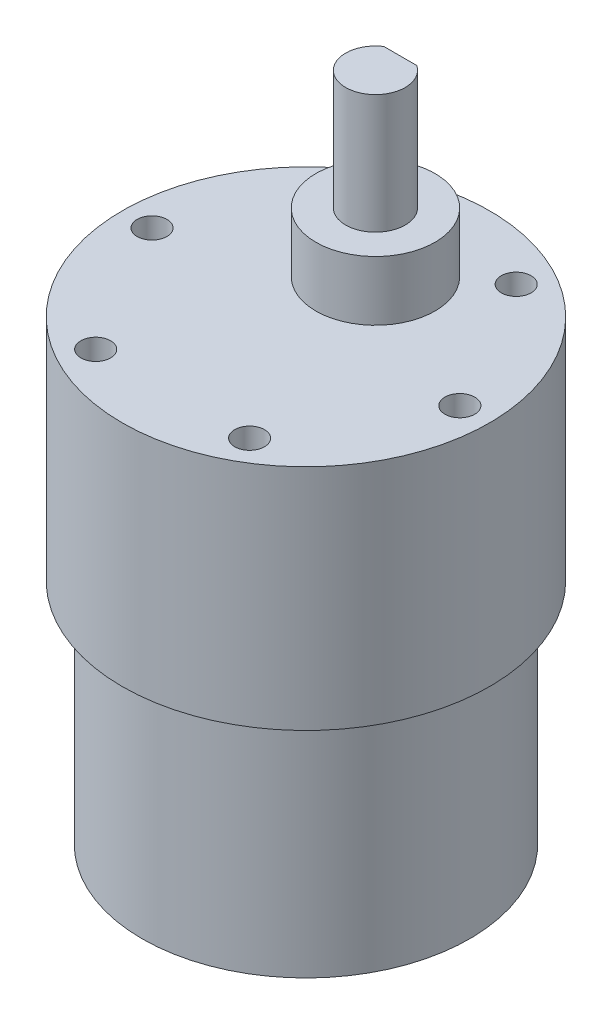
SolidWorks part; units mm, degrees
ref_plane "前视基准面" through (0, 0, 0) normal (0, 0, 1) x (1, 0, 0)
ref_plane "上视基准面" through (0, 0, 0) normal (0, 1, 0) x (1, 0, 0)
ref_plane "右视基准面" through (0, 0, 0) normal (1, 0, 0) x (0, 0, -1)
sketch "草图1" plane through (0, 0, 0) normal (0, 1, 0) x (1, 0, 0)
  circle A0 centre (0, 0) radius 16.5
  circle A1 centre (0, 0) radius 18.5
  dimension "D1" = 33
  dimension "D2" = 37
extrude "凸台-拉伸1" add sketch "草图1" against normal blind 23 contours A0
extrude "凸台-拉伸2" add sketch "草图1<3>" along normal blind 23 contours A1
sketch "草图1<3>" plane through (0, 0, 0) normal (0, 1, 0) x (1, 0, 0) same geometry as "草图1"
sketch "草图3" plane through (0, 23, 0) normal (0, 1, 0) x (1, 0, 0)
  line L0 (0, 18.5) -> (0, -18.5) construction
  line L2 (7.75, -13.4234) -> (15.5, 0) construction
  line L3 (15.5, 0) -> (7.75, 13.4234) construction
  line L4 (7.75, 13.4234) -> (-7.75, 13.4234) construction
  line L5 (-7.75, 13.4234) -> (-15.5, 0) construction
  line L6 (-15.5, 0) -> (-7.75, -13.4234) construction
  line L7 (-7.75, -13.4234) -> (7.75, -13.4234) construction
  circle A0 centre (0, 0) radius 18.5 construction
  circle A1 centre (0, 7) radius 6
  circle A2 centre (0, 7) radius 3
  circle A3 centre (0, 0) radius 15.5 construction
  circle A4 centre (-7.75, 13.4234) radius 1.5
  circle A5 centre (7.75, 13.4234) radius 1.5
  circle A6 centre (15.5, 0) radius 1.5
  circle A7 centre (7.75, -13.4234) radius 1.5
  circle A8 centre (-7.75, -13.4234) radius 1.5
  circle A9 centre (-15.5, 0) radius 1.5
  point P29 (0, 0)
  dimension "D1" = 7
  dimension "D2" = 12
  dimension "D3" = 6
  dimension "D4" = 6
  dimension "D5" = 31
  dimension "D6" = 30
extrude "切除-拉伸1" cut sketch "草图3" against normal blind 2.5 contours A4 | A9 | A8 | A7 | A6 | A5
extrude "凸台-拉伸3" add sketch "草图3<3>" along normal blind 18 contours A2
sketch "草图3<3>" plane through (0, 23, 0) normal (0, 1, 0) x (1, 0, 0) same geometry as "草图3"
extrude "凸台-拉伸4" add sketch "草图3<4>" along normal blind 6 contours A1
sketch "草图3<4>" plane through (0, 23, 0) normal (0, 1, 0) x (1, 0, 0) same geometry as "草图3"
sketch "草图4" plane through (0, 41, 0) normal (0, 1, 0) x (1, 0, 0)
  line L0 (-1.6583, 9.5) -> (1.6583, 9.5)
  arc A0 (1.6583, 9.5) -> (-1.6583, 9.5) centre (0, 7) ccw
  dimension "D1" = 2.5
extrude "切除-拉伸2" cut sketch "草图4" against normal blind 12
sketch "草图5" plane through (0, -23, 0) normal (0, -1, 0) x (1, 0, 0)
  circle A0 centre (0, 0) radius 5.7642
